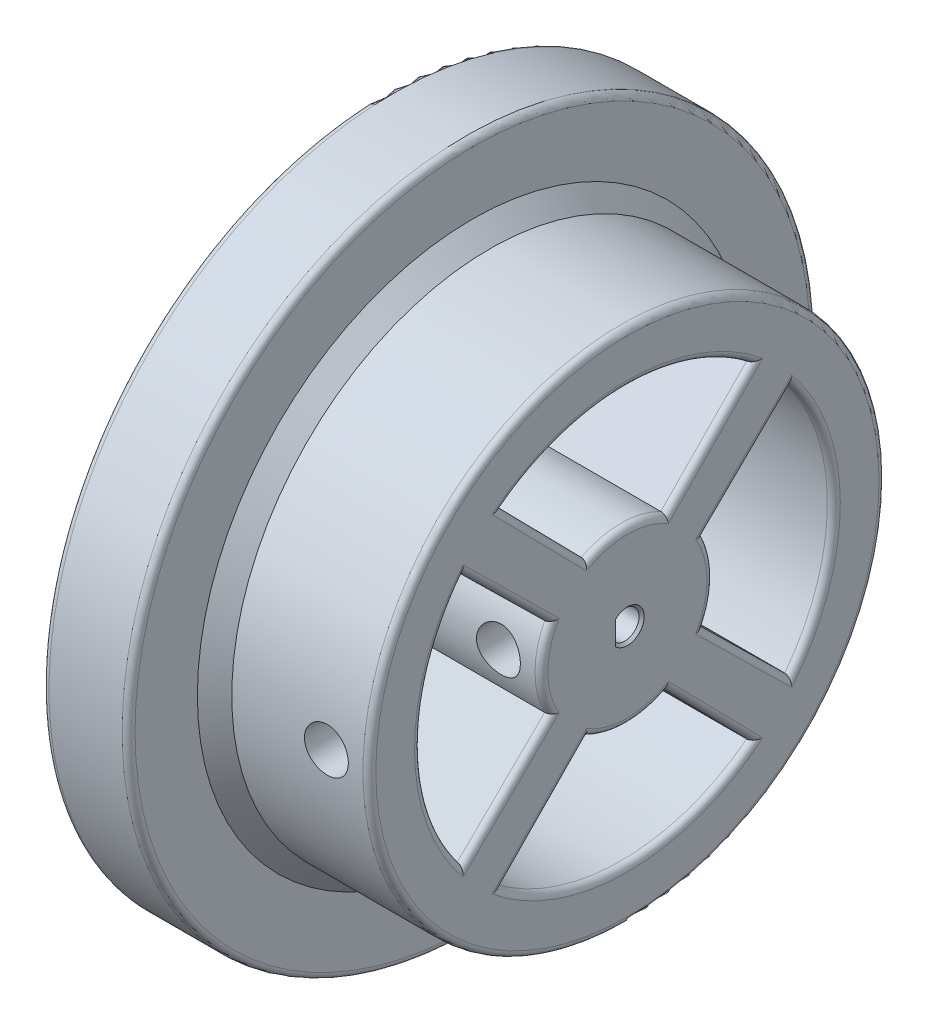
SolidWorks part; units mm, degrees
ref_plane "Front Plane" through (0, 0, 0) normal (0, 0, 1) x (1, 0, 0)
ref_plane "Top Plane" through (0, 0, 0) normal (0, 1, 0) x (1, 0, 0)
ref_plane "Right Plane" through (0, 0, 0) normal (1, 0, 0) x (0, 0, -1)
sketch "Sketch1" plane through (0, 0, 0) normal (1, 0, 0) x (0, 0, -1)
  circle A0 centre (0, 0) radius 40
  dimension "D1" = 80
extrude "Boss-Extrude1" add sketch "Sketch1" along normal blind 10 contours A0
sketch "Sketch2" plane through (10, 0, 0) normal (1, 0, 0) x (0, 0, -1)
  circle A0 centre (0, 0) radius 30
  dimension "D1" = 60
extrude "Boss-Extrude2" add sketch "Sketch2" along normal blind 18
sketch "Sketch5" plane through (28, 0, 0) normal (1, 0, 0) x (0, 0, -1)
  line L0 (-1.1, 1.2298) -> (-1.1, -1.2298)
  line L1 (1.65, -1.2522) -> (1.65, 1.7565) construction
  arc A0 (-1.1, -1.2298) -> (-1.1, 1.2298) centre (0, 0) ccw
  dimension "D1" = 3.3
  dimension "D2" = 2.75
extrude "Cut-Extrude1" cut sketch "Sketch5" against normal blind 12
sketch "Sketch6" plane through (28, 0, 0) normal (1, 0, 0) x (0, 0, -1)
  line L2 (4.624, 8.8667) -> (14.612, 19.0391)
  line L7 (4.2426, 0) -> (0, -4.2426) construction
  line L8 (4.2426, 0) -> (0, 4.2426) construction
  line L9 (0, 4.2426) -> (-4.2426, 0) construction
  line L13 (0, -4.2426) -> (-4.2426, 0) construction
  line L14 (4.2426, 0) -> (-4.2426, 0) construction
  line L15 (0, 4.2426) -> (0, -4.2426) construction
  line L16 (8.8667, 4.624) -> (19.0391, 14.612)
  line L17 (-8.8667, -4.624) -> (-19.0391, -14.612)
  line L18 (-4.624, -8.8667) -> (-14.612, -19.0391)
  line L19 (4.624, -8.8667) -> (14.612, -19.0391)
  line L20 (8.8667, -4.624) -> (19.0391, -14.612)
  line L21 (-4.624, 8.8667) -> (-14.612, 19.0391)
  line L22 (-8.8667, 4.624) -> (-19.0391, 14.612)
  arc A1 (14.612, 19.0391) -> (0, 24) centre (0, 0) ccw
  arc A2 (-2.9514, 23.8178) -> (-14.612, 19.0391) centre (0, 0) ccw
  arc A3 (19.0391, -14.612) -> (19.0391, 14.612) centre (0, 0) ccw
  arc A4 (-14.612, -19.0391) -> (14.612, -19.0391) centre (0, 0) ccw
  circle A5 centre (0, 0) radius 24.9521
  arc A6 (0, 24) -> (-2.9514, 23.8178) centre (0, 0) ccw
  arc A7 (-8.8667, 4.624) -> (-8.8667, -4.624) centre (0, 0) ccw
  arc A8 (4.624, 8.8667) -> (-4.624, 8.8667) centre (0, 0) ccw
  arc A9 (8.8667, -4.624) -> (8.8667, 4.624) centre (0, 0) ccw
  arc A10 (-4.624, -8.8667) -> (4.624, -8.8667) centre (0, 0) ccw
  arc A11 (-19.0391, 14.612) -> (-19.0391, -14.612) centre (0, 0) ccw
  dimension "D1" = 20
  dimension "D2" = 48
  dimension "D4" = 6
  dimension "D5" = 6
extrude "Cut-Extrude2" cut sketch "Sketch6" against normal up to next contours A1 | A3 | A4 | A2 | L22 A11 L17 A7 region at (28, 17.1038, 0) region at (28, 0, -17.1038) region at (28, -17.1038, 0)
ref_plane "Plane1" through (0, 0, 30) normal (0, 0, 1) x (1, 0, 0)
sketch "Sketch8" plane through (0, 0, 30) normal (0, 0, 1) x (1, 0, 0)
  line L0 (28, 0) -> (23, 0) construction
  line L1 (28, -30) -> (28, 30) construction
  line L2 (55, 0) -> (-55, 0) construction
  circle A0 centre (23, 0) radius 2.55
  dimension "D2" = 5.1
  dimension "D1" = 5
extrude "Cut-Extrude3" cut sketch "Sketch8" against normal blind 29.7 contours A0
chamfer "Chamfer1" distance 0.3 angle 45 2 edges at (28, 0, 1.1) (28, 0, -1.65)
sketch "Sketch9" plane through (0, 0, 0) normal (0, 0, 1) x (1, 0, 0)
  line L0 (10, 40) -> (0, 40) construction
  line L1 (0, -55) -> (0, 55) construction
  line L2 (1.75, 40) -> (8.25, 40)
  line L3 (8.25, 40) -> (8.25, 39.5)
  line L4 (5, 40) -> (5, 36.6496) construction
  line L5 (8.25, 39.5) -> (1.75, 39.5)
  line L6 (1.75, 40) -> (1.75, 39.5)
  line L7 (19, 30) -> (19, 25.6089) construction
  line L8 (28, 30) -> (10, 30) construction
  line L9 (13, 30) -> (25, 30)
  line L10 (25, 30) -> (25, 29.5)
  line L11 (25, 29.5) -> (13, 29.5)
  line L12 (13, 30) -> (13, 29.5)
  point P12 (5, 39.5)
  point P20 (19, 29.5)
  dimension "D1" = 3.25
  dimension "D2" = 0.5
  dimension "D3" = 6
  dimension "D4" = 0.5
ref_axis "X axis" through (31.5, 0, 0) along (-1, 0, 0)
chamfer "Chamfer2" distance 2 angle 45 1 edges at (10, 0, -30)
fillet "Fillet1" radius 0.75 17 edges at (28, -13.9529, -9.618) (28, -10, 0) (28, -13.9529, 9.618) (28, -24, 0) (28, 0, -24) (28, -9.618, -13.9529) (28, 0, -10) (28, 9.618, -13.9529) (28, 13.9529, -9.618) (28, 10, 0) (28, 24, 0) (28, 13.9529, 9.618) (28, 0, -30) (28, 9.618, 13.9529) (28, 0, 10) (28, -9.618, 13.9529) (28, 0, 24)
fillet "Fillet3" radius 0.75 18 edges at (0, -13.9529, -9.618) (0, -24, 0) (0, -13.9529, 9.618) (0, -10, 0) (0, -9.618, 13.9529) (0, 0, 24) (0, 9.618, 13.9529) (0, 0, 10) (0, 0, -40) (0, 13.9529, 9.618) (0, 24, 0) (0, 13.9529, -9.618) (0, 10, 0) (0, 9.618, -13.9529) (0, 0, -24) (0, -9.618, -13.9529) (0, 0, -10) (10, 0, -40)
sketch "Sketch10" plane through (0, 0, 0) normal (-1, 0, 0) x (0, 0, 1)
  circle A0 centre (0, 0) radius 30 construction
  text T0 "'ey, dis mighty lissard man can swing his sword so fast, dat it's more dan da speed a sound!" font "Century Gothic" height 2.8
  dimension "D1" = 60
